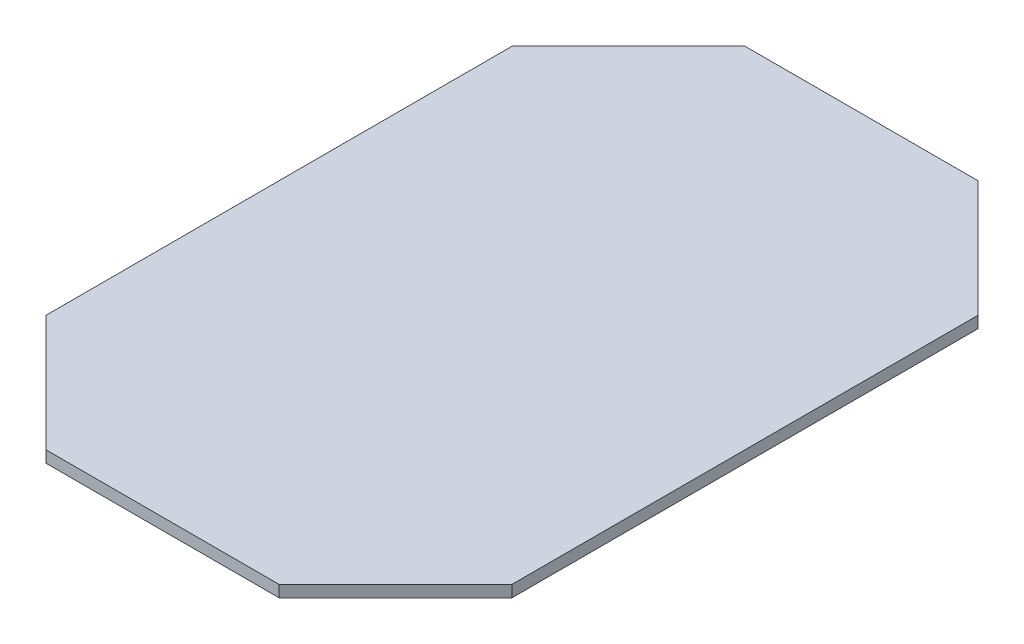
SolidWorks part; units mm, degrees
ref_plane "Front Plane" through (0, 0, 0) normal (0, 0, 1) x (1, 0, 0)
ref_plane "Top Plane" through (0, 0, 0) normal (0, 1, 0) x (1, 0, 0)
ref_plane "Right Plane" through (0, 0, 0) normal (1, 0, 0) x (0, 0, -1)
ref_axis "X" through (-88.99, 0, 0) along (1, 0, 0)
ref_axis "Y" through (0, 55, 0) along (0, -1, 0)
ref_axis "Z" through (0, 0, -88.99) along (0, 0, 1)
sketch "Sketch1" plane through (0, 0, 0) normal (0, 1, 0) x (1, 0, 0)
  line L0 (-40, 40) -> (-20, 60)
  line L1 (-40, 40) -> (40, 40)
  line L2 (-40, 40) -> (-40, -40)
  line L3 (-40, -40) -> (40, -40)
  line L4 (40, 40) -> (40, -40)
  line L5 (-40, 40) -> (40, -40) construction
  line L6 (-40, -40) -> (40, 40) construction
  line L7 (-20, 60) -> (20, 60)
  line L8 (20, 60) -> (40, 40)
  line L9 (0, 60) -> (0, 40) construction
  line L10 (0, 0) -> (-40, 0) construction
  line L11 (0, -60) -> (0, -40) construction
  line L12 (20, -60) -> (40, -40)
  line L13 (-20, -60) -> (20, -60)
  line L14 (-40, -40) -> (-20, -60)
  point P0 (0, 0)
  point P10 (0, 40)
  dimension "D1" = 80
  dimension "D2" = 80
  dimension "D3" = 20
  dimension "D4" = 40
extrude "Boss-Extrude1" add sketch "Sketch1" along normal blind 2 contours L4 L1 L2 L3 | L8 L7 L0 L1 | L3 L14 L13 L12 region at (0, 0, -48.8889) region at (0, 0, 0) region at (0, 0, 48.8889)
